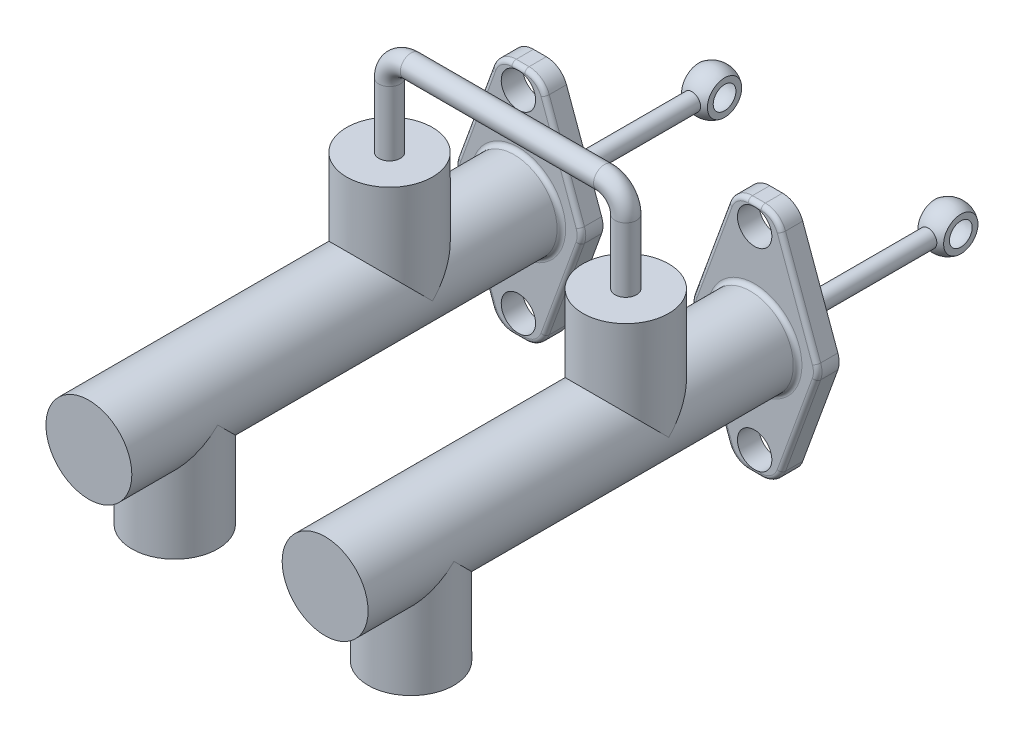
SolidWorks part; units mm, degrees
ref_plane "Płaszczyzna przednia" through (0, 0, 0) normal (0, 0, 1) x (1, 0, 0)
ref_plane "Płaszczyzna górna" through (0, 0, 0) normal (0, 1, 0) x (1, 0, 0)
ref_plane "Płaszczyzna prawa" through (0, 0, 0) normal (1, 0, 0) x (0, 0, -1)
sketch "Szkic1" plane through (0, 0, 0) normal (0, 0, 1) x (1, 0, 0)
  line L0 (0, 0) -> (0, 14.8807) construction
  circle A0 centre (-27.5, 0) radius 10
  circle A1 centre (27.5, 0) radius 10
  point P4 (0, 0)
  dimension "D1" = 20
  dimension "D2" = 55
extrude "Dodanie-wyciągnięcie1" add sketch "Szkic1" along normal mid plane 100
sketch "Szkic2" plane through (0, 0, -50) normal (0, 0, -1) x (-1, 0, 0)
  line L0 (-22.5, 27.5) -> (-32.5, 27.5)
  line L1 (-32.5, 27.5) -> (-42.5, 0)
  line L2 (-42.5, 0) -> (-32.5, -27.5)
  line L3 (-32.5, -27.5) -> (-22.5, -27.5)
  line L4 (-22.5, -27.5) -> (-12.5, 0)
  line L5 (-12.5, 0) -> (-22.5, 27.5)
  line L6 (-27.5, 0) -> (-27.5, 40.9003) construction
  line L7 (-27.5, 0) -> (-56.3461, 0) construction
  line L8 (0, 0) -> (0, 40.9003) construction
  line L9 (27.5, 0) -> (56.3461, 0) construction
  line L10 (27.5, 0) -> (27.5, 40.9003) construction
  line L11 (12.5, 0) -> (22.5, 27.5)
  line L12 (22.5, -27.5) -> (12.5, 0)
  line L13 (32.5, -27.5) -> (22.5, -27.5)
  line L14 (42.5, 0) -> (32.5, -27.5)
  line L15 (32.5, 27.5) -> (42.5, 0)
  line L16 (22.5, 27.5) -> (32.5, 27.5)
  circle A0 centre (-27.5, 22.5) radius 4
  circle A1 centre (-27.5, -22.5) radius 4
  circle A2 centre (27.5, -22.5) radius 4
  circle A3 centre (27.5, 22.5) radius 4
  dimension "D4" = 45
  dimension "D5" = 8
  dimension "D1" = 10
  dimension "D2" = 30
  dimension "D3" = 55
extrude "Dodanie-wyciągnięcie2" add sketch "Szkic2" along normal blind 5
fillet "Zaokrąglenie1" radius 5 6 edges at (-22.5, 27.5, -52.5) (-12.5, 0, -52.5) (-22.5, -27.5, -52.5) (-32.5, -27.5, -52.5) (-42.5, 0, -52.5) (-32.5, 27.5, -52.5)
fillet "Zaokrąglenie2" radius 5 6 edges at (12.5, 0, -52.5) (22.5, -27.5, -52.5) (32.5, -27.5, -52.5) (42.5, 0, -52.5) (32.5, 27.5, -52.5) (22.5, 27.5, -52.5)
fillet "Zaokrąglenie3" radius 1 13 edges at (-12.8203, 0, -50) (-17.2123, 12.9587, -50) (-23.1337, 26.5953, -50) (-31.8663, 26.5953, -50) (-37.7877, 12.9587, -50) (-42.1797, 0, -50) (-37.7877, -12.9587, -50) (-31.8663, -26.5953, -50) (-23.1337, -26.5953, -50) (-17.2123, -12.9587, -50) (-17.5, 0, -50) (-27.5, 27.5, -50) (-27.5, -27.5, -50)
fillet "Zaokrąglenie4" radius 1 13 edges at (42.1797, 0, -50) (37.7877, 12.9587, -50) (31.8663, 26.5953, -50) (27.5, 27.5, -50) (23.1337, 26.5953, -50) (17.2123, 12.9587, -50) (12.8203, 0, -50) (17.2123, -12.9587, -50) (23.1337, -26.5953, -50) (27.5, -27.5, -50) (31.8663, -26.5953, -50) (37.7877, -12.9587, -50) (37.5, 0, -50)
sketch "Szkic3" plane through (0, 0, 0) normal (0, 1, 0) x (1, 0, 0)
  line L0 (27.5, -50) -> (27.5, 106.4766) construction
  line L6 (17.5, -50) -> (37.5, -50) construction
  line L7 (31.5, 55) -> (23.5, 55) construction
  line L8 (27.5, 55) -> (29.5, 55)
  line L9 (27.5, 55) -> (27.5, 91)
  line L11 (29.5, 55) -> (29.5, 90.4174)
  line L14 (27.5, 99) -> (27.5, 100)
  arc A0 (27.5, 91) -> (27.5, 99) centre (27.5, 95) ccw
  arc A1 (29.5, 90.4174) -> (27.5, 100) centre (27.5, 95) ccw
  dimension "D3" = 8
  dimension "D4" = 10
  dimension "D1" = 2
  dimension "D2" = 40
revolve "Obrót1" add sketch "Szkic3" angle 360 about L0
sketch "Szkic4" plane through (0, 0, 0) normal (0, 1, 0) x (1, 0, 0)
  line L0 (-27.5, -50) -> (-27.5, 310.5537) construction
  line L1 (-37.5, -50) -> (-17.5, -50) construction
  line L2 (-28.9979, 55) -> (-26.0021, 55) construction
  line L3 (-27.5, 55) -> (-29.5, 55)
  line L4 (-27.5, 55) -> (-27.5, 91)
  line L6 (-29.5, 55) -> (-29.5, 90.4174)
  line L7 (-27.5, 99) -> (-27.5, 100)
  arc A0 (-27.5, 99) -> (-27.5, 91) centre (-27.5, 95) ccw
  arc A1 (-27.5, 100) -> (-29.5, 90.4174) centre (-27.5, 95) ccw
  dimension "D3" = 8
  dimension "D4" = 10
  dimension "D1" = 40
  dimension "D2" = 2
revolve "Obrót2" add sketch "Szkic4" angle 360 about L0
sketch "Szkic5" plane through (0, 0, -55) normal (0, 0, -1) x (-1, 0, 0)
  line L1 (-30.5, -10) -> (-24.5, -10)
  line L2 (-30.5, -10) -> (-30.5, 10)
  line L3 (-30.5, 10) -> (-24.5, 10)
  line L4 (-24.5, -10) -> (-24.5, 10)
  line L5 (-30.5, -10) -> (-24.5, 10) construction
  line L6 (-30.5, 10) -> (-24.5, -10) construction
  line L11 (-33.5, -12.5) -> (-21.5, -12.5)
  line L12 (-33.5, -12.5) -> (-33.5, 12.5)
  line L13 (-33.5, 12.5) -> (-21.5, 12.5)
  line L14 (-21.5, -12.5) -> (-21.5, 12.5)
  line L15 (-33.5, -12.5) -> (-21.5, 12.5) construction
  line L16 (-33.5, 12.5) -> (-21.5, -12.5) construction
  line L17 (24.5, -10) -> (30.5, -10)
  line L18 (24.5, -10) -> (24.5, 10)
  line L19 (24.5, 10) -> (30.5, 10)
  line L20 (30.5, -10) -> (30.5, 10)
  line L21 (24.5, -10) -> (30.5, 10) construction
  line L22 (24.5, 10) -> (30.5, -10) construction
  line L23 (21.5, -12.5) -> (33.5, -12.5)
  line L24 (21.5, -12.5) -> (21.5, 12.5)
  line L25 (21.5, 12.5) -> (33.5, 12.5)
  line L26 (33.5, -12.5) -> (33.5, 12.5)
  line L27 (21.5, -12.5) -> (33.5, 12.5) construction
  line L28 (21.5, 12.5) -> (33.5, -12.5) construction
  point P0 (-27.5, 0)
  point P5 (-27.5, 0)
  point P6 (-27.5, 0)
  point P12 (27.5, 0)
  point P17 (27.5, 0)
  dimension "D1" = 6
  dimension "D2" = 20
  dimension "D3" = 12
  dimension "D4" = 25
  dimension "D5" = 6
  dimension "D6" = 20
  dimension "D7" = 12
  dimension "D8" = 25
extrude "Wytnij-wyciągnięcie1" cut sketch "Szkic5" along normal blind 50
sketch "Szkic6" plane through (0, 0, 0) normal (0, 1, 0) x (1, 0, 0)
  line L0 (-37.5, 49) -> (-37.5, -50) construction
  line L1 (-17.5, -50) -> (-17.5, 49) construction
  line L2 (0, 0) -> (0, 36.7421) construction
  line L3 (-38.5, 50) -> (-16.5, 50) construction
  circle A0 centre (-27.5, 20) radius 10
  circle A1 centre (27.5, 20) radius 10
  point P8 (0, 0)
  dimension "D1" = 30
extrude "Dodanie-wyciągnięcie3" add sketch "Szkic6" along normal blind 25
ref_plane "Płaszczyzna1" through (0, 0, -20) normal (0, 0, 1) x (1, 0, 0)
sketch "Szkic7" plane through (0, 0, -20) normal (0, 0, 1) x (1, 0, 0)
  line L0 (-27.5, 25) -> (-27.5, 40)
  line L1 (-22.5, 45) -> (22.5, 45)
  line L2 (27.5, 40) -> (27.5, 25)
  line L3 (-17.5, 25) -> (-37.5, 25) construction
  line L4 (37.5, 25) -> (17.5, 25) construction
  arc A0 (22.5, 45) -> (27.5, 40) centre (22.5, 40) cw
  arc A1 (-22.5, 45) -> (-27.5, 40) centre (-22.5, 40) ccw
  point P4 (0, 0)
  point P7 (0, 0)
  point P14 (-27.5, 45)
  dimension "D2" = 5
  dimension "D1" = 20
sweep "Wyciągnięcie po ścieżce1" add path "Szkic7" circular profile diameter 5 parameters "D3"=5
sketch "Szkic19" plane through (0, 0, 0) normal (0, 1, 0) x (1, 0, 0)
  line L0 (17.5, 20) -> (17.5, -50) construction
  line L1 (37.5, -50) -> (37.5, 20) construction
  line L2 (-37.5, 20) -> (-37.5, -50) construction
  line L3 (-17.5, -50) -> (-17.5, 20) construction
  line L4 (-37.5, -50) -> (-17.5, -50) construction
  circle A0 centre (27.5, -30) radius 10
  circle A1 centre (-27.5, -30) radius 10
  circle A2 centre (-27.5, -30) radius 6
  circle A3 centre (27.5, -30) radius 6
  point P15 (0, 0)
  dimension "D1" = 20
  dimension "D2" = 12
extrude "Dodanie-wyciągnięcie4" add sketch "Szkic19" against normal blind 25
